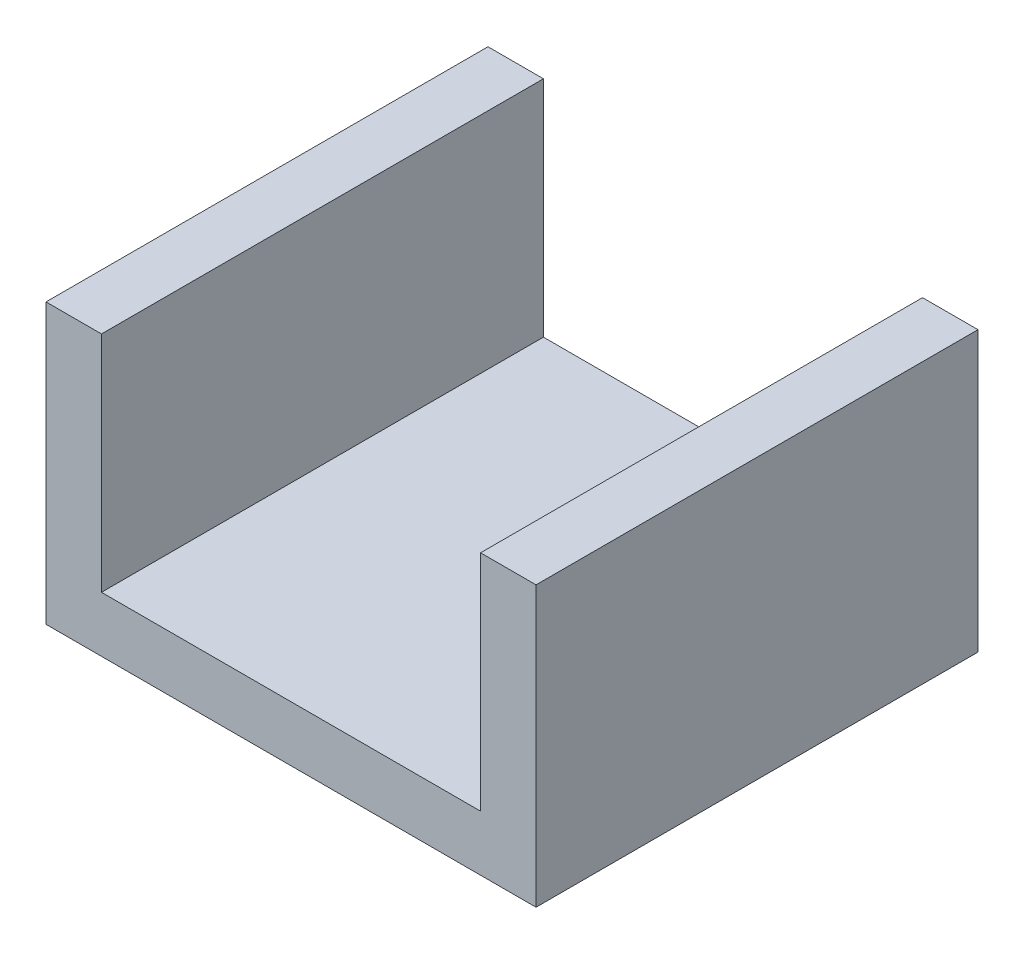
SolidWorks part; units mm, degrees
ref_plane "Front Plane" through (0, 0, 0) normal (0, 0, 1) x (1, 0, 0)
ref_plane "Top Plane" through (0, 0, 0) normal (0, 1, 0) x (1, 0, 0)
ref_plane "Right Plane" through (0, 0, 0) normal (1, 0, 0) x (0, 0, -1)
sketch "Sketch1" plane through (0, 0, 0) normal (0, 1, 0) x (1, 0, 0)
  line L0 (10.25, 0) -> (10.25, -23.9)
  line L1 (0, 0) -> (20.5, 0)
  line L2 (0, 0) -> (0, -23.9)
  line L3 (0, -23.9) -> (20.5, -23.9)
  line L4 (20.5, 0) -> (20.5, -23.9)
  line L5 (0, 0) -> (4.3752, 0)
  line L6 (0, 0) -> (0, -23.9)
  line L7 (0, -23.9) -> (4.3752, -23.9)
  line L9 (20.5, 0) -> (20.5, -23.9)
  line L10 (20.5, -23.9) -> (16.1248, -23.9)
  line L11 (20.5, 0) -> (20.5, -23.9)
  line L12 (20.5, 0) -> (16.1248, 0)
  line L13 (0, 0) -> (-3, 0)
  line L14 (0, 0) -> (0, -23.9)
  line L15 (0, -23.9) -> (-3, -23.9)
  line L16 (-3, 0) -> (-3, -23.9)
  line L17 (20.5, -23.9) -> (23.5, -23.9)
  line L18 (23.5, 0) -> (23.5, -23.9)
  line L19 (20.5, 0) -> (23.5, 0)
  dimension "D1" = 23.9
  dimension "D2" = 20.5
  dimension "D4" = 4.3752
  dimension "D6" = 3
extrude "Boss-Extrude1" add sketch "Sketch1" along normal blind 3 contours L1 L3 L4 | L1 L0 L3 | L1 L3 L0 | L1 L2 L3 | L13 L16 L15 L2 | L19 L4 L17 L18 region at (15.375, 0, 11.95) region at (5.125, 0, 11.95) region at (-1.5, 0, 11.95) region at (22, 0, 11.95)
extrude "Boss-Extrude2" add sketch "Sketch1<3>" along normal blind 15.1 contours L13 L16 L15 L2 | L19 L4 L17 L18 region at (-1.5, 0, 11.95) region at (22, 0, 11.95)
sketch "Sketch1<3>" plane through (0, 0, 0) normal (0, 1, 0) x (1, 0, 0) same geometry as "Sketch1"
